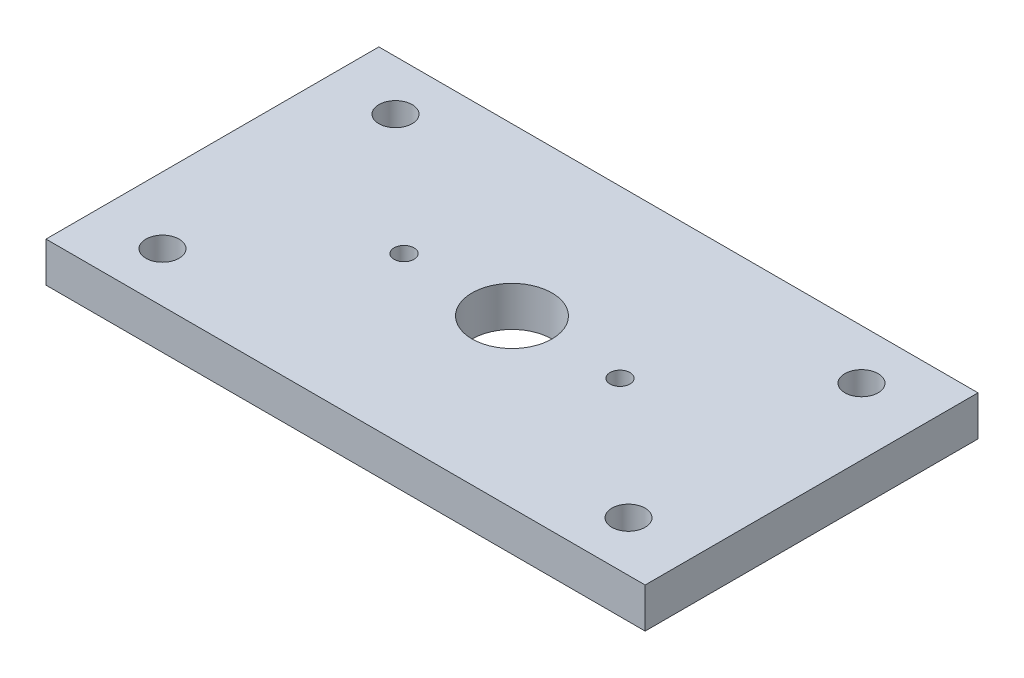
SolidWorks part; units mm, degrees
ref_plane "Front Plane" through (0, 0, 0) normal (0, 0, 1) x (1, 0, 0)
ref_plane "Top Plane" through (0, 0, 0) normal (0, 1, 0) x (1, 0, 0)
ref_plane "Right Plane" through (0, 0, 0) normal (1, 0, 0) x (0, 0, -1)
sketch "Sketch1" plane through (0, 0, 0) normal (0, 1, 0) x (1, 0, 0)
  line L0 (0, -55) -> (0, 55) construction
  line L5 (-55, 0) -> (55, 0) construction
  line L6 (-45, 25) -> (45, 25)
  line L7 (-45, 25) -> (-45, -25)
  line L8 (-45, -25) -> (45, -25)
  line L9 (45, 25) -> (45, -25)
  line L10 (-45, 25) -> (45, -25) construction
  line L11 (-45, -25) -> (45, 25) construction
  circle A0 centre (0, 0) radius 6
  circle A1 centre (0, 0) radius 16.22 construction
  circle A2 centre (-16.22, 0) radius 1.5
  circle A3 centre (16.22, 0) radius 1.5
  circle A4 centre (-35, 17.5) radius 2.5
  circle A5 centre (35, 17.5) radius 2.5
  circle A6 centre (35, -17.5) radius 2.5
  circle A7 centre (-35, -17.5) radius 2.5
  point P27 (-91.9503, 30.6883)
  point P28 (-92.1511, 52.1856)
  dimension "D1" = 12
  dimension "D2" = 32.44
  dimension "D3" = 3
  dimension "D4" = 5
  dimension "D5" = 50
  dimension "D6" = 35
  dimension "D7" = 90
  dimension "D8" = 17.5
extrude "Boss-Extrude1" add sketch "Sketch1" along normal blind 6
sketch "Sketch2" plane through (0, 0, 0) normal (0, 1, 0) x (1, 0, 0)
  line L0 (0, -55) -> (0, 55) construction
  line L1 (-55, 0) -> (55, 0) construction
  circle A0 centre (-35, 17.5) radius 6
  circle A1 centre (35, 17.5) radius 6
  circle A2 centre (35, -17.5) radius 6
  circle A3 centre (-35, -17.5) radius 6
  dimension "D1" = 12
extrude "Cut-Extrude2" cut sketch "Sketch2" along normal blind 1.5
